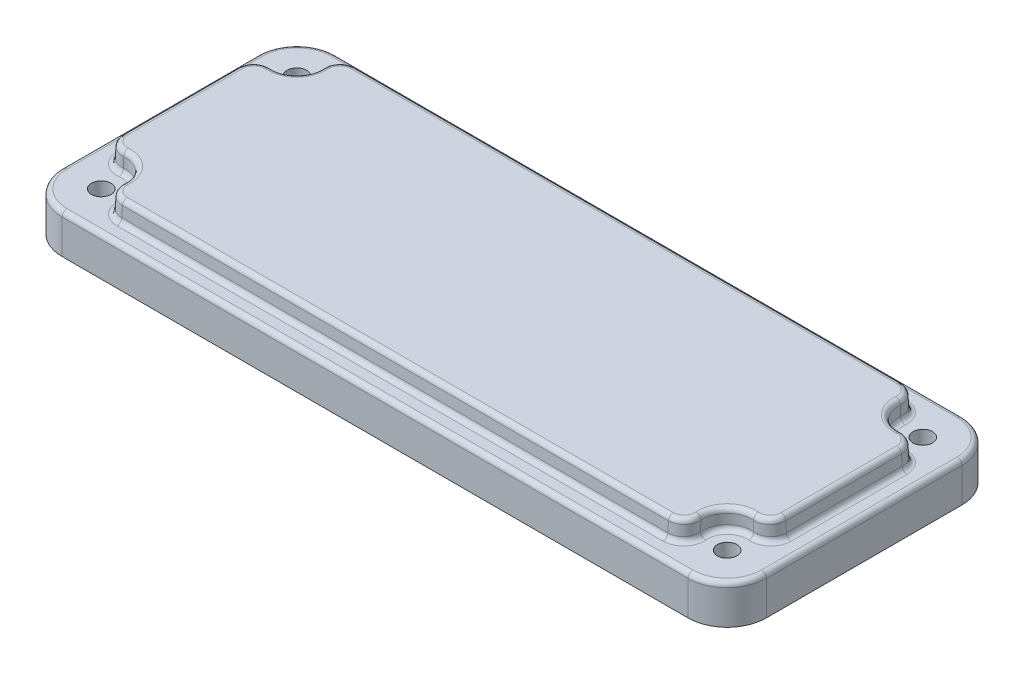
SolidWorks part; units mm, degrees
material "PW20:29:Sc:0:"
ref_plane "Front" through (0, 0, 0) normal (0, 0, 1) x (1, 0, 0)
ref_plane "Top" through (0, 0, 0) normal (0, 1, 0) x (1, 0, 0)
ref_plane "Right" through (0, 0, 0) normal (1, 0, 0) x (0, 0, -1)
sketch "Sketch1" plane through (0, 0, 0) normal (0, 1, 0) x (1, 0, 0)
  line L0 (-50.8, 22.225) -> (50.8, 22.225)
  line L1 (-57.15, 15.875) -> (-57.15, -15.875)
  line L2 (50.8, -22.225) -> (-50.8, -22.225)
  line L3 (57.15, -15.875) -> (57.15, 15.875)
  line L4 (-50.8, -15.875) -> (50.8, 15.875) construction
  arc A0 (-57.15, -15.875) -> (-50.8, -22.225) centre (-50.8, -15.875) ccw
  arc A1 (57.15, -15.875) -> (50.8, -22.225) centre (50.8, -15.875) cw
  arc A2 (50.8, 22.225) -> (57.15, 15.875) centre (50.8, 15.875) cw
  arc A3 (-50.8, 22.225) -> (-57.15, 15.875) centre (-50.8, 15.875) ccw
  dimension "D1" = 114.3
  dimension "D2" = 44.45
  dimension "D4" = 6.35
extrude "Base-Extrude" add sketch "Sketch1" along normal blind 6.35
sketch "Sketch2" plane through (0, 6.35, 0) normal (0, 1, 0) x (-1, 0, 0)
  line L4 (50.8, 19.05) -> (-50.8, 19.05)
  line L5 (-53.975, 15.875) -> (-53.975, -15.875)
  line L6 (-50.8, -19.05) -> (50.8, -19.05)
  line L7 (53.975, -15.875) -> (53.975, 15.875)
  line L8 (50.8, 19.05) -> (-50.8, 19.05)
  line L9 (-53.975, 15.875) -> (-53.975, -15.875)
  line L10 (-50.8, -19.05) -> (50.8, -19.05)
  line L11 (53.975, -15.875) -> (53.975, 15.875)
  arc A4 (53.975, 15.875) -> (50.8, 19.05) centre (50.8, 15.875) ccw
  arc A5 (53.975, 15.875) -> (50.8, 19.05) centre (50.8, 15.875) ccw
  arc A6 (-50.8, 19.05) -> (-53.975, 15.875) centre (-50.8, 15.875) ccw
  arc A7 (-50.8, 19.05) -> (-53.975, 15.875) centre (-50.8, 15.875) ccw
  arc A8 (-53.975, -15.875) -> (-50.8, -19.05) centre (-50.8, -15.875) ccw
  arc A9 (-53.975, -15.875) -> (-50.8, -19.05) centre (-50.8, -15.875) ccw
  arc A10 (50.8, -19.05) -> (53.975, -15.875) centre (50.8, -15.875) ccw
  arc A11 (50.8, -19.05) -> (53.975, -15.875) centre (50.8, -15.875) ccw
  dimension "D1" = 3.175
extrude "Boss-Extrude1" add sketch "Sketch2" along normal blind 3.175 draft 3
sketch "Sketch3" plane through (0, 9.525, 0) normal (0, 1, 0) x (-1, 0, 0)
  circle A0 centre (-50.8, 15.875) radius 3.9687
  dimension "D1" = 7.9375
extrude "Cut-Extrude1" cut sketch "Sketch3" against normal up to surface (3.175 mm away)
sketch "Sketch4" plane through (0, 6.35, 0) normal (0, 1, 0) x (-1, 0, 0)
  circle A0 centre (-50.8, 15.875) radius 1.5875
  dimension "D1" = 3.175
extrude "Cut-Extrude2" cut sketch "Sketch4" against normal through all
mirror "Mirror1" about plane through (0, 0, 0) normal (0, 0, 1) of "Cut-Extrude2", "Cut-Extrude1"
mirror "Mirror2" about plane through (0, 0, 0) normal (1, 0, 0) of "Mirror1"
fillet "Fillet1" radius 2.54 8 edges at (48.3138, 7.9044, 18.9685) (53.8935, 7.9044, 13.3888) (53.8935, 7.9044, -13.3888) (48.3138, 7.9044, -18.9685) (-48.3138, 7.9044, -18.9685) (-53.8935, 7.9044, -13.3888) (-53.8935, 7.9044, 13.3888) (-48.3138, 7.9044, 18.9685)
fillet "Fillet2" radius 0.7937 40 edges at (0, 6.35, -19.05) (0, 9.525, -18.8836) (-46.2625, 6.35, -18.1482) (46.1444, 6.35, -18.2787) (-45.8933, 9.525, -18.3276) (46.3986, 9.525, -17.785) (-47.9937, 6.35, -13.0687) (47.9937, 6.35, -13.0687) (-47.9937, 9.525, -13.0687) (47.9937, 9.525, -13.0687) (-53.2213, 6.35, -11.2022) (53.0648, 6.35, -11.3446) (-52.71, 9.525, -11.4736) (53.2526, 9.525, -10.9683) (0, 6.35, -22.225) (-53.975, 6.35, 0) (53.975, 6.35, 0) (-53.8086, 9.525, 0) (53.8086, 9.525, 0) (55.2901, 6.35, -20.3651) (-55.2901, 6.35, -20.3651) (-53.0383, 6.35, 11.3664) (53.2408, 6.35, 11.1827) (-53.2526, 9.525, 10.9683) (52.71, 9.525, 11.4736) (57.15, 6.35, 0) (-57.15, 6.35, 0) (-47.9937, 6.35, 13.0687) (47.9937, 6.35, 13.0687) (-47.9937, 9.525, 13.0687) (47.9937, 9.525, 13.0687) (55.2901, 6.35, 20.3651) (-55.2901, 6.35, 20.3651) (-46.1066, 6.35, 18.3169) (46.2919, 6.35, 18.1127) (-46.3986, 9.525, 17.785) (45.8933, 9.525, 18.3276) (0, 6.35, 22.225) (0, 6.35, 19.05) (0, 9.525, 18.8836)
sketch "Sketch5" plane through (0, 0, 0) normal (0, -1, 0) x (1, 0, 0)
  line L0 (-44.45, 15.875) -> (44.45, 15.875)
  line L1 (-44.45, 15.875) -> (-44.45, -15.875)
  line L2 (44.45, -15.875) -> (-44.45, -15.875)
  line L3 (44.45, -15.875) -> (44.45, 15.875)
  line L4 (50.8, 22.225) -> (-50.8, 22.225) construction
  line L5 (57.15, 15.875) -> (57.15, -15.875) construction
  line L6 (-57.15, -15.875) -> (-57.15, 15.875) construction
  line L7 (-50.8, -22.225) -> (50.8, -22.225) construction
  dimension "D1" = 6.35
  dimension "D2" = 12.7
  dimension "D3" = 12.7
  dimension "D4" = 6.35
extrude "Cut-Extrude3" cut sketch "Sketch5" against normal blind 6.35 draft 3
fillet "Fillet3" radius 6.35 4 edges at (44.2836, 3.175, 15.7086) (44.2836, 3.175, -15.7086) (-44.2836, 3.175, 15.7086) (-44.2836, 3.175, -15.7086)
fillet "Fillet4" radius 3.175 8 edges at (44.1172, 6.35, 0) (42.2609, 6.35, 13.6859) (42.2609, 6.35, -13.6859) (0, 6.35, 15.5422) (0, 6.35, -15.5422) (-42.2609, 6.35, 13.6859) (-42.2609, 6.35, -13.6859) (-44.1172, 6.35, 0)
sketch "Sketch6" plane through (0, 9.525, 0) normal (0, 1, 0) x (-1, 0, 0)
  circle A0 centre (0, 0) radius 3.175
  dimension "Diam" = 6.35
extrude "Boss-Extrude2" [suppressed] add sketch "Sketch6" along normal blind 12.7
sketch "Sketch7" [suppressed] plane through (0, 0, 0) normal (1, 0, 0) x (0, 0, -1)
  line L0 (-21.4313, 30.1625) -> (15.875, 30.1625) construction
  line L1 (0, 22.225) -> (0, 9.525) construction
  line L2 (3.175, 22.225) -> (-3.175, 22.225) construction
  circle A0 centre (0, 22.225) radius 3.175
  dimension "D1" = 9.525
  dimension "Diam" = 6.35
revolve "Boss-Revolve1" [suppressed] add sketch "Sketch7" angle 360 about L0
fillet "Fillet5" [suppressed] radius 2.032
